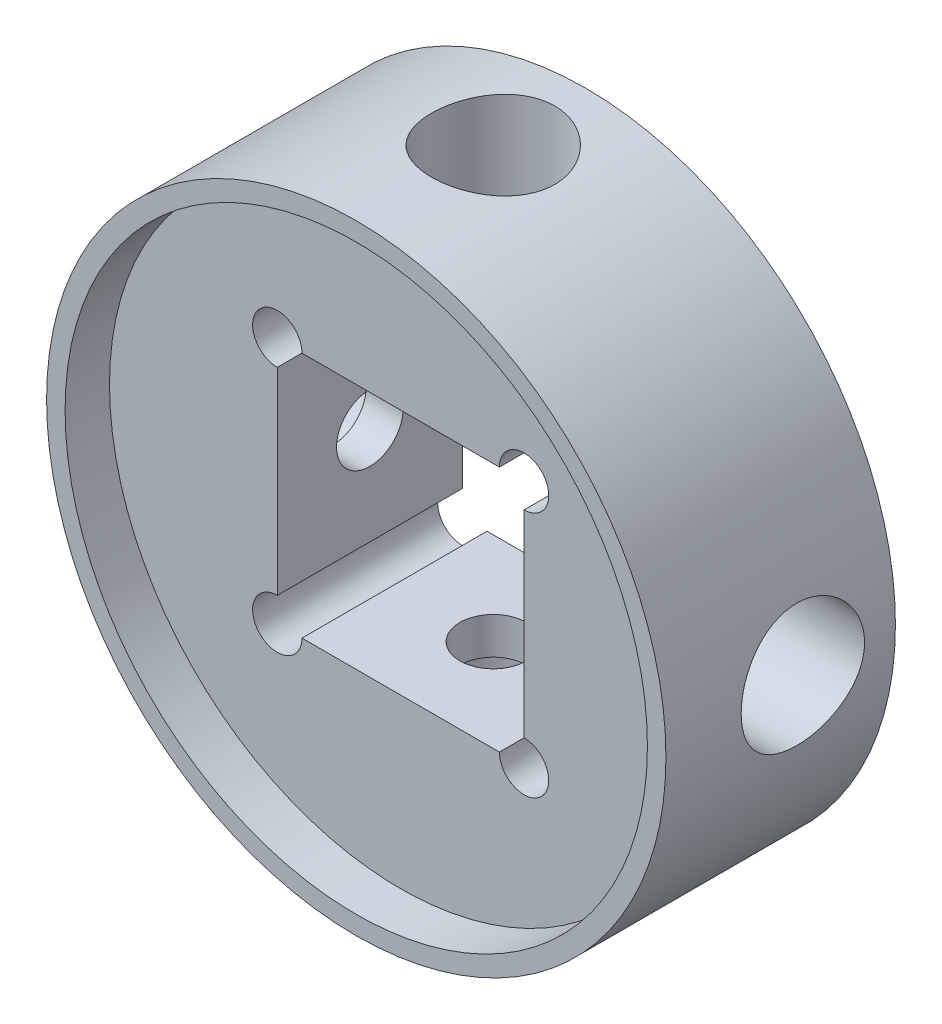
SolidWorks part; units mm, degrees
material "S235JR"
ref_plane "xy" through (0, 0, 0) normal (0, 0, 1) x (1, 0, 0)
ref_plane "xz" through (0, 0, 0) normal (0, 1, 0) x (1, 0, 0)
ref_plane "yz" through (0, 0, 0) normal (1, 0, 0) x (0, 0, -1)
ref_axis "x" through (-88.99, 0, 0) along (1, 0, 0)
ref_axis "y" through (0, 55, 0) along (0, -1, 0)
ref_axis "z" through (0, 0, -88.99) along (0, 0, 1)
sketch "Skizze1" plane through (0, 0, 0) normal (0, 0, 1) x (1, 0, 0)
  line L1 (-10, 10) -> (10, 10)
  line L2 (-10, 10) -> (-10, -10)
  line L3 (-10, -10) -> (10, -10)
  line L4 (10, 10) -> (10, -10)
  circle A0 centre (0, 0) radius 25.1
  point P7 (0, 10)
  point P8 (-10, 0)
  dimension "D2" = 50.2
  dimension "D1" = 20
extrude "Aufsatz-Linear austragen1" add sketch "Skizze1" along normal blind 15
sketch "Skizze2" plane through (0, 0, 15) normal (0, 0, 1) x (1, 0, 0)
  circle A0 centre (0, 0) radius 23.6
  circle A1 centre (0, 0) radius 25.1
  circle A2 centre (0, 0) radius 25.1
  dimension "D2" = 47.2
  dimension "D1" = 0
extrude "Aufsatz-Linear austragen2" add sketch "Skizze2" along normal blind 3.6
sketch "Skizze3" plane through (0, 0, 0) normal (0, 0, 1) x (1, 0, 0)
  circle A0 centre (-10, 10) radius 2
  circle A1 centre (10, 10) radius 2
  circle A2 centre (10, -10) radius 2
  circle A3 centre (-10, -10) radius 2
  dimension "D1" = 4
extrude "Schnitt-Linear austragen2" cut sketch "Skizze3" along normal through all
sketch "Skizze4" plane through (0, 0, 0) normal (0, 1, 0) x (1, 0, 0)
  line L0 (8, -15) -> (-8, 0) construction
  circle A0 centre (0, -7.5) radius 2.7
  circle A1 centre (0, -7.5) radius 5
  dimension "D1" = 5.4
  dimension "D2" = 10
extrude "Schnitt-Linear austragen3" cut sketch "Skizze4" against normal through all and the other way through all contours A0
sketch "Skizze5" plane through (0, 0, 0) normal (1, 0, 0) x (0, 0, -1)
  circle A0 centre (-7.5, 0) radius 2.7
  circle A1 centre (-7.5, 0) radius 5
  dimension "D1" = 5.4
  dimension "D2" = 10
extrude "Schnitt-Linear austragen4" cut sketch "Skizze5" against normal through all and the other way through all contours A0
extrude "Schnitt-Linear austragen5" cut sketch "Skizze4<3>" along normal through all from offset 13 contours A1
sketch "Skizze4<3>" plane through (0, 0, 0) normal (0, 1, 0) x (1, 0, 0) same geometry as "Skizze4"
mirror "Spiegeln1" about plane through (0, 0, 0) normal (0, 1, 0) of "Schnitt-Linear austragen5"
extrude "Schnitt-Linear austragen6" cut sketch "Skizze5<3>" along normal through all from offset 13 contours A1
sketch "Skizze5<3>" plane through (0, 0, 0) normal (1, 0, 0) x (0, 0, -1) same geometry as "Skizze5"
mirror "Spiegeln2" about plane through (0, 0, 0) normal (1, 0, 0) of "Schnitt-Linear austragen6"
